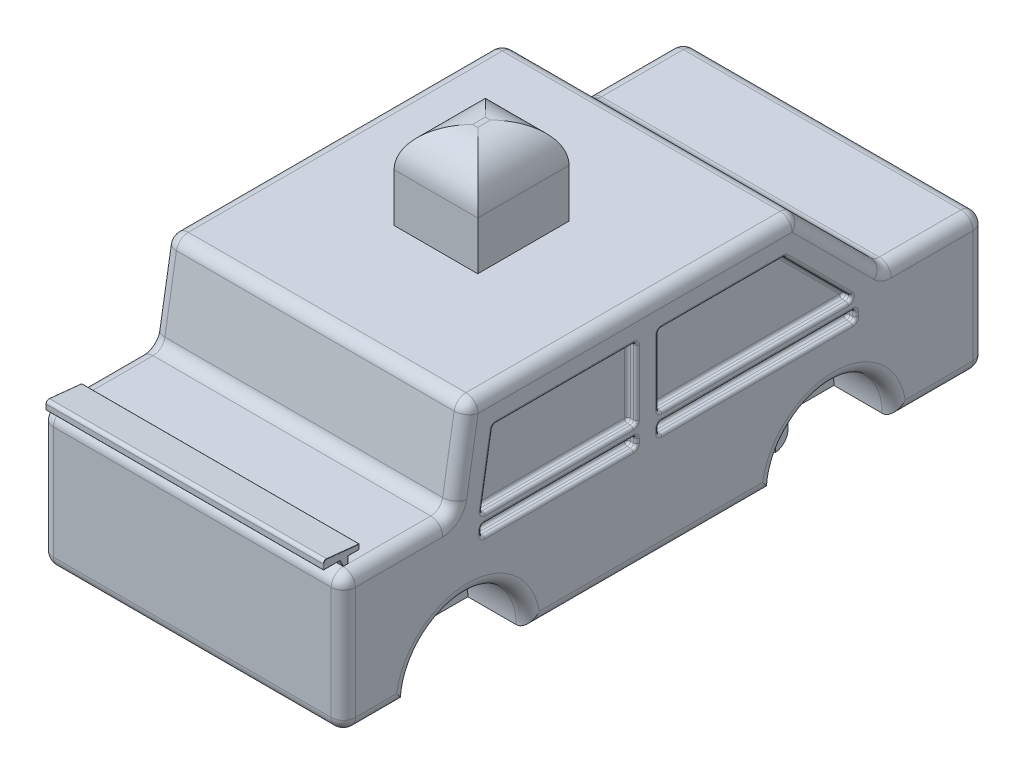
SolidWorks part; units mm, degrees
ref_plane "Front Plane" through (0, 0, 0) normal (0, 0, 1) x (1, 0, 0)
ref_plane "Top Plane" through (0, 0, 0) normal (0, 1, 0) x (1, 0, 0)
ref_plane "Right Plane" through (0, 0, 0) normal (1, 0, 0) x (0, 0, -1)
sketch "Sketch1" plane through (0, 0, 0) normal (1, 0, 0) x (0, 0, -1)
  line L0 (0, 0) -> (-21.2859, 0)
  line L1 (-82.5718, 0) -> (-82.5718, 45.3421)
  line L2 (-82.5718, 45.3421) -> (-46.2112, 45.3421)
  line L3 (-46.2112, 45.3421) -> (-41.2859, 74.8941)
  line L4 (-41.2859, 74.8941) -> (67.7958, 74.8941)
  line L5 (67.7958, 74.8941) -> (97.3478, 45.3421)
  line L6 (97.3478, 45.3421) -> (130.0868, 45.3421)
  line L7 (130.0868, 45.3421) -> (130.0868, 0)
  line L8 (130.0868, 0) -> (100, 0)
  line L9 (-61.2859, 0) -> (-82.5718, 0)
  line L10 (60, 0) -> (0, 0)
  arc A0 (100, 0) -> (60, 0) centre (80, 0) ccw
  arc A1 (-21.2859, 0) -> (-61.2859, 0) centre (-41.2859, 0) ccw
extrude "Boss-Extrude1" add sketch "Sketch1" along normal mid plane 100
ref_plane "Plane1" through (30, 0, 0) normal (1, 0, 0) x (0, 0, -1)
sketch "Sketch2" plane through (30, 0, 0) normal (1, 0, 0) x (0, 0, -1)
  line L0 (-21.2859, 0) -> (-38.2859, 0)
  line L1 (-61.2859, 0) -> (-61.2859, 3.8294)
  line L2 (-61.2859, 3.8294) -> (-21.2859, 3.8294)
  line L3 (-21.2859, 3.8294) -> (-21.2859, 0)
  line L4 (-41.2859, 10.667) -> (-41.2859, 0) construction
  line L5 (-38.2859, -3) -> (-38.2859, 0)
  line L6 (-44.2859, -3) -> (-44.2859, 0)
  line L7 (-44.2859, 0) -> (-61.2859, 0)
  line L8 (-41.2859, -1) -> (-41.2859, -12.6401) construction
  arc A2 (-44.2859, -3) -> (-38.2859, -3) centre (-41.2859, -3) ccw
  circle A3 centre (-41.2859, -3) radius 2
sketch "Sketch3" plane through (30, 0, 0) normal (1, 0, 0) x (0, 0, -1)
  line L0 (60, 0) -> (75.174, 0)
  line L1 (100, 0) -> (100, 4.8047)
  line L2 (100, 4.8047) -> (60, 4.8047)
  line L3 (60, 4.8047) -> (60, 0)
  line L4 (80, 12.3629) -> (80, -5.8559) construction
  line L5 (75.174, -4.826) -> (75.174, 0)
  line L6 (84.826, -4.826) -> (84.826, 0)
  line L7 (84.826, 0) -> (100, 0)
  line L8 (79.404, -7.1008) -> (79.404, -9.615)
  line L10 (80, -7.1775) -> (80, -9.6519) construction
  line L11 (80.596, -7.1008) -> (80.596, -9.615)
  arc A0 (80.596, -9.615) -> (84.826, -4.826) centre (80, -4.826) ccw
  arc A1 (75.174, -4.826) -> (79.404, -9.615) centre (80, -4.826) ccw
  arc A2 (80.596, -7.1008) -> (79.404, -7.1008) centre (80, -4.826) ccw
extrude "Boss-Extrude3" add sketch "Sketch3" against normal blind 5
extrude "Boss-Extrude4" add sketch "Sketch2" against normal blind 5
mirror "Mirror5" about plane through (0, 0, 0) normal (1, 0, 0) of "Boss-Extrude4", "Boss-Extrude3"
sketch "Sketch4" plane through (0, 74.8941, 0) normal (0, 1, 0) x (1, 0, 0)
  line L0 (-50, 67.7958) -> (50, -41.2859) construction
  line L1 (-50, -41.2859) -> (50, 67.7958) construction
  line L3 (13.8588, -1.8625) -> (-13.8588, -1.8625)
  line L4 (13.8588, -1.8625) -> (13.8588, 28.3724)
  line L5 (13.8588, 28.3724) -> (-13.8588, 28.3724)
  line L6 (-13.8588, -1.8625) -> (-13.8588, 28.3724)
  line L7 (13.8588, -1.8625) -> (-13.8588, 28.3724) construction
  line L8 (13.8588, 28.3724) -> (-13.8588, -1.8625) construction
  point P8 (0, 13.2549)
extrude "Boss-Extrude5" add sketch "Sketch4" along normal blind 29
fillet "Fillet1" radius 13 4 edges at (0, 103.8941, -28.3724) (13.8588, 103.8941, -13.2549) (0, 103.8941, 1.8625) (-13.8588, 103.8941, -13.2549)
fillet "Fillet4" radius 4 32 edges at (0, 45.3421, 82.5718) (0, 0, 82.5718) (0, 74.8941, 41.2859) (0, 45.3421, 46.2112) (0, 74.8941, -67.7958) (0, 45.3421, -97.3478) (0, 0, -130.0868) (0, 45.3421, -130.0868) (-50, 0, -115.0434) (-50, 22.671, -130.0868) (-50, 45.3421, -113.7173) (-50, 60.1181, -82.5718) (-50, 74.8941, -13.2549) (-50, 60.1181, 43.7486) (-50, 45.3421, 64.3915) (-50, 22.671, 82.5718) (-50, 0, 71.9288) (-50, 20, 41.2859) (-50, 0, -19.3571) (-50, 20, -80) (50, 20, 41.2859) (50, 0, 71.9288) (50, 22.671, 82.5718) (50, 45.3421, 64.3915) (50, 60.1181, 43.7486) (50, 74.8941, -13.2549) (50, 60.1181, -82.5718) (50, 45.3421, -113.7173) (50, 22.671, -130.0868) (50, 0, -115.0434) (50, 20, -80) (50, 0, -19.3571)
sketch "Sketch5" plane through (0, 0, -130.0868) normal (0, 0, -1) x (-1, 0, 0)
  line L0 (-46, 30.3322) -> (46, 30.3322) construction
  line L1 (-46, 41.3421) -> (-46, 4) construction
  line L2 (46, 4) -> (46, 41.3421) construction
  line L3 (46, 32.7878) -> (-46, 32.7878) construction
  line L4 (0, 32.7878) -> (0, 23.3987) construction
  line L5 (39.4736, 32.7878) -> (32.9367, 32.7878)
  line L6 (-39.4736, 32.7878) -> (-32.9367, 32.7878)
  arc A0 (32.9367, 32.7878) -> (39.4736, 32.7878) centre (36.2051, 30.3322) ccw
  arc A1 (-32.9367, 32.7878) -> (-39.4736, 32.7878) centre (-36.2051, 30.3322) cw
extrude "Cut-Extrude1" cut sketch "Sketch5" against normal blind 6
sketch "Sketch6" plane through (50, 0, 0) normal (1, 0, 0) x (0, 0, -1)
  line L0 (-36.74, 41.3421) -> (14.5596, 41.3421)
  line L1 (87.2057, 41.3421) -> (63.6537, 64.8941)
  line L2 (63.6537, 64.8941) -> (21.9053, 64.8941)
  line L3 (-36.74, 41.3421) -> (-32.8146, 64.8941)
  line L4 (66.1389, 70.8941) -> (-37.8974, 70.8941) construction
  line L5 (-37.8974, 70.8941) -> (-41.7086, 48.0269) construction
  line L6 (93.3478, 43.6852) -> (66.1389, 70.8941) construction
  line L7 (14.5596, 64.8941) -> (14.5596, 41.3421)
  line L8 (21.9053, 41.3421) -> (21.9053, 64.8941)
  line L9 (14.5596, 64.8941) -> (-32.8146, 64.8941)
  line L10 (21.9053, 41.3421) -> (87.2057, 41.3421)
  line L11 (14.5596, 38.1331) -> (-36.74, 38.1331)
  line L12 (-36.74, 38.1331) -> (-36.74, 34.734)
  line L13 (-36.74, 34.734) -> (14.5596, 34.734)
  line L14 (87.2057, 34.734) -> (87.2057, 38.1331)
  line L15 (87.2057, 38.1331) -> (21.9053, 38.1331)
  line L16 (21.9053, 38.1331) -> (21.9053, 34.734)
  line L17 (14.5596, 38.1331) -> (14.5596, 34.734)
  line L18 (21.9053, 34.734) -> (87.2057, 34.734)
  dimension "D1" = 6
  dimension "D2" = 6
  dimension "D3" = 6
extrude "Cut-Extrude2" cut sketch "Sketch6" against normal blind 3
fillet "Fillet5" radius 1 48 edges at (47, 53.1181, -14.5596) (47, 41.3421, 11.0902) (47, 53.1181, 34.7773) (47, 53.1181, -21.9053) (47, 64.8941, -42.7795) (47, 53.1181, -75.4297) (47, 41.3421, -54.5555) (50, 64.8941, 9.1275) (50, 53.1181, -75.4297) (50, 41.3421, -54.5555) (50, 53.1181, -21.9053) (50, 64.8941, -42.7795) (50, 53.1181, -14.5596) (47, 64.8941, 9.1275) (50, 53.1181, 34.7773) (50, 41.3421, 11.0902) (48.5, 41.3421, -87.2057) (48.5, 64.8941, -63.6537) (48.5, 64.8941, -21.9053) (48.5, 41.3421, -21.9053) (48.5, 41.3421, -14.5596) (48.5, 64.8941, -14.5596) (48.5, 41.3421, 36.74) (48.5, 64.8941, 32.8146) (50, 34.734, 11.0902) (50, 38.1331, 11.0902) (50, 38.1331, -54.5555) (50, 34.734, -54.5555) (48.5, 38.1331, 36.74) (48.5, 34.734, 36.74) (50, 36.4336, 36.74) (47, 34.734, 11.0902) (47, 36.4336, 36.74) (47, 38.1331, 11.0902) (48.5, 34.734, -14.5596) (47, 36.4336, -14.5596) (48.5, 38.1331, -14.5596) (50, 36.4336, -14.5596) (48.5, 34.734, -87.2057) (48.5, 38.1331, -87.2057) (50, 36.4336, -87.2057) (48.5, 38.1331, -21.9053) (48.5, 34.734, -21.9053) (50, 36.4336, -21.9053) (47, 36.4336, -21.9053) (47, 38.1331, -54.5555) (47, 36.4336, -87.2057) (47, 34.734, -54.5555)
sketch "Sketch7" plane through (0, 71.3449, -71.3449) normal (0, 0.7071, -0.7071) x (1, 0, 0)
  line L0 (-46, 35.1168) -> (-46, -3.3624)
  line L1 (-46, -3.3624) -> (46, -3.3624)
  line L2 (46, -3.3624) -> (46, 35.1168)
  line L3 (46, 35.1168) -> (-46, 35.1168)
  line L4 (44, 33.1168) -> (-44, 33.1168)
  line L5 (-44, 33.1168) -> (-44, -1.3624)
  line L6 (-44, -1.3624) -> (44, -1.3624)
  line L7 (44, -1.3624) -> (44, 33.1168)
  line L8 (42, 31.1168) -> (-42, 31.1168)
  line L9 (-42, 31.1168) -> (-42, 0.6376)
  line L10 (-42, 0.6376) -> (42, 0.6376)
  line L11 (42, 0.6376) -> (42, 31.1168)
  dimension "D1" = 2
  dimension "D2" = 2
extrude "Cut-Extrude3" cut sketch "Sketch7" against normal blind 3 contours L10 L11 L8 L9 | L6 L7 L4 L5 L11 L10 L9 L8 region at (43.0549, 60.1181, -82.5718) region at (0, 60.1181, -82.5718)
fillet "Fillet6" radius 1 12 edges at (0, 47.9278, -94.762) (0, 72.3083, -70.3816) (44, 71.2476, -69.3209) (44, 46.8672, -93.7014) (44, 60.1181, -82.5718) (-44, 46.8672, -93.7014) (-44, 71.2476, -69.3209) (-44, 60.1181, -82.5718) (-44, 57.9967, -80.4505) (0, 45.8065, -92.6407) (44, 57.9967, -80.4505) (0, 70.187, -68.2603)
fillet "Fillet7" radius 0.2 4 edges at (36.2051, 26.244, -130.0868) (36.2051, 32.7878, -130.0868) (-36.2051, 26.244, -130.0868) (-36.2051, 32.7878, -130.0868)
ref_plane "Plane2" through (46, 0, 0) normal (1, 0, 0) x (0, 0, -1)
sketch "Sketch8" plane through (46, 0, 0) normal (1, 0, 0) x (0, 0, -1)
  line L0 (-78.5718, 45.3421) -> (-79.6909, 47.5347)
  line L1 (-79.6909, 47.5347) -> (-85.1139, 47.5347)
  line L2 (-85.1139, 47.5347) -> (-85.1139, 49.2668)
  line L3 (-84.0112, 50.2615) -> (-73.235, 49.1487)
  line L4 (-73.235, 49.1487) -> (-73.235, 47.5347)
  line L5 (-73.235, 47.5347) -> (-76.9834, 47.5347)
  line L6 (-76.9834, 47.5347) -> (-76.9834, 45.3421)
  line L7 (-78.5718, 45.3421) -> (-49.5997, 45.3421) construction
  line L8 (-76.9834, 45.3421) -> (-78.5718, 45.3421)
  arc A0 (-85.1139, 49.2668) -> (-84.0112, 50.2615) centre (-84.1139, 49.2668) cw
  dimension "D1" = 1
extrude "Boss-Extrude6" add sketch "Sketch8" against normal blind 92 contours L1 L2 A0 L3 L4 L5 L6 L8 L0
fillet "Fillet8" radius 0.1 21 edges at (-46, 46.4384, 79.1314) (46, 46.4384, 79.1314) (-46, 46.4384, 76.9834) (46, 46.4384, 76.9834) (-46, 48.4008, 85.1139) (-46, 50.0093, 84.7837) (46, 48.4008, 85.1139) (46, 50.0093, 84.7837) (-46, 49.7051, 78.6231) (46, 49.7051, 78.6231) (0, 47.5347, 79.6909) (-46, 47.5347, 82.4024) (0, 47.5347, 85.1139) (46, 47.5347, 82.4024) (-46, 47.5347, 75.1092) (0, 47.5347, 76.9834) (46, 47.5347, 75.1092) (0, 49.1487, 73.235) (-46, 48.3417, 73.235) (0, 47.5347, 73.235) (46, 48.3417, 73.235)
